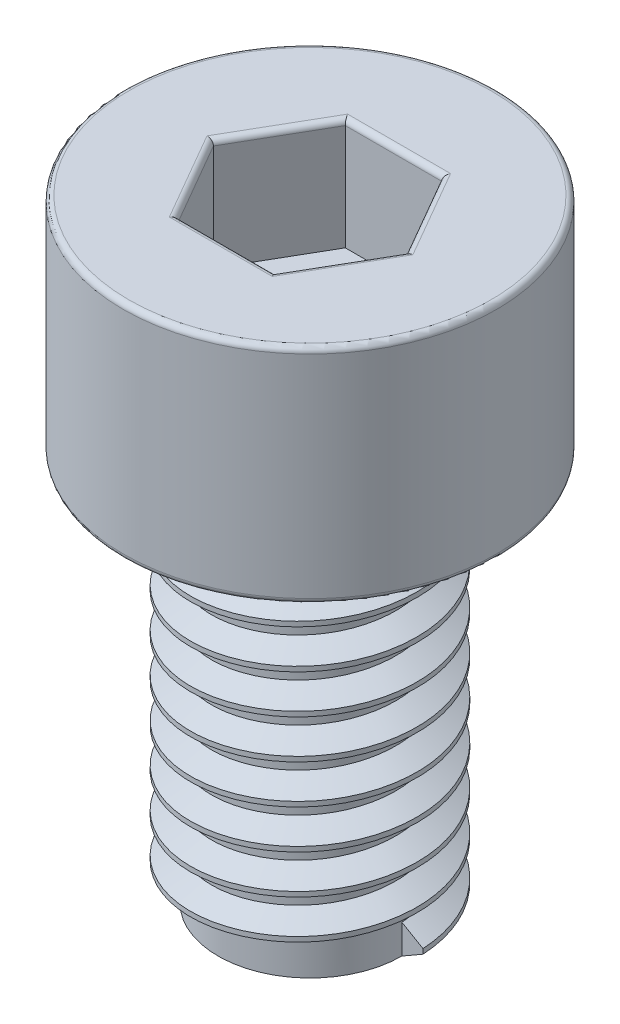
SolidWorks part; units mm, degrees
ref_plane "Front Plane" through (0, 0, 0) normal (0, 0, 1) x (1, 0, 0)
ref_plane "Top Plane" through (0, 0, 0) normal (0, 1, 0) x (1, 0, 0)
ref_plane "Right Plane" through (0, 0, 0) normal (1, 0, 0) x (0, 0, -1)
sketch "Sketch1" plane through (0, 0, 0) normal (0, 1, 0) x (1, 0, 0)
  circle A0 centre (0, 0) radius 1.65
  dimension "D1" = 3.3
extrude "Boss-Extrude1" add sketch "Sketch1" against normal blind 7
sketch "Sketch2" plane through (0, 0, 0) normal (0, 1, 0) x (1, 0, 0)
  circle A0 centre (0, 0) radius 3.35
  dimension "D1" = 6.7
extrude "Boss-Extrude2" add sketch "Sketch2" along normal blind 4
thread "Thread1" pitch 0.7 method extrude profile "Thread Profile1" start angle 0, offset 0, length 0, pitch 0.7, diameter 3.3
ref_plane "Plane1" through (1.65, -7, 0) normal (0, 0, 1) x (1, 0, 0)
sketch "Thread Profile1" plane through (1.65, -7, 0) normal (0, 0, 1) x (1, 0, 0)
  line L0 (0, 0) -> (0, 0.7) construction
  line L1 (0, 0) -> (0.3789, 0.2187)
  line L2 (0.3789, 0.2187) -> (0.3789, 0.3062)
  line L3 (0.3789, 0.3062) -> (0, 0.525)
  line L4 (0.3789, 0.2625) -> (0, 0.2625) construction
  line L11 (0, 0) -> (0, 0.525)
  point P2 (0, 0)
  dimension "Pitch" = 0.7
  dimension "Profile_Angle" = 60
  dimension "Profile_Land" = 0.0875
  dimension "Profile_Height" = 0.3789
sketch "Sketch7" plane through (0, 4, 0) normal (0, 1, 0) x (1, 0, 0)
  line L1 (1.7321, 0) -> (0.866, 1.5)
  line L2 (0.866, 1.5) -> (-0.866, 1.5)
  line L3 (-0.866, 1.5) -> (-1.7321, 0)
  line L4 (-1.7321, 0) -> (-0.866, -1.5)
  line L5 (-0.866, -1.5) -> (0.866, -1.5)
  line L6 (0.866, -1.5) -> (1.7321, 0)
  circle A0 centre (0, 0) radius 1.5 construction
  dimension "D1" = 3
  dimension "D2" = 1.5
extrude "Cut-Extrude1" cut sketch "Sketch7" against normal blind 2
fillet "Fillet1" radius 0.1 8 edges at (0, 0, 3.35) (0, 4, 3.35) (1.299, 4, -0.75) (0, 4, -1.5) (-1.299, 4, -0.75) (-1.299, 4, 0.75) (0, 4, 1.5) (1.299, 4, 0.75)
